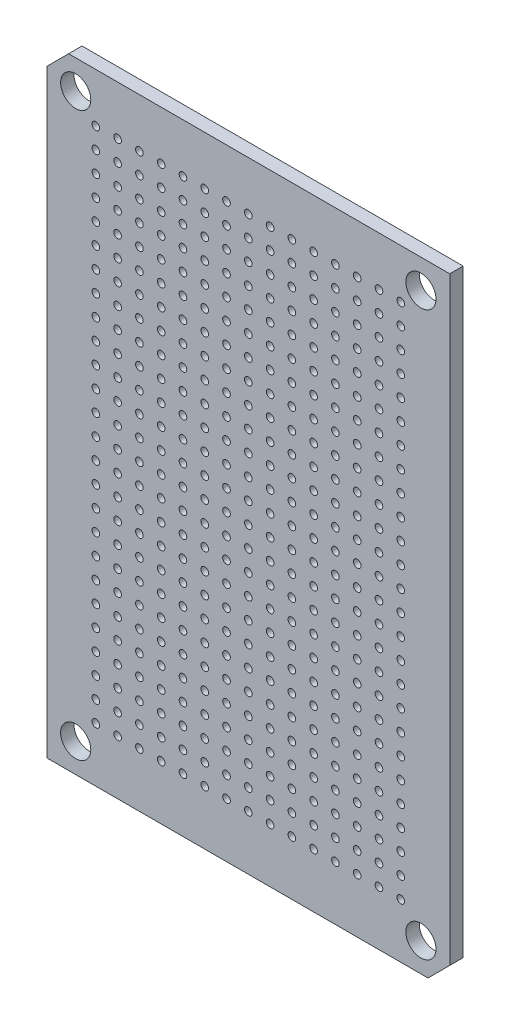
SolidWorks part; units mm, degrees
ref_plane "Front Plane" through (0, 0, 0) normal (0, 0, 1) x (1, 0, 0)
ref_plane "Top Plane" through (0, 0, 0) normal (0, 1, 0) x (1, 0, 0)
ref_plane "Right Plane" through (0, 0, 0) normal (1, 0, 0) x (0, 0, -1)
sketch "Sketch1" plane through (0, 0, 0) normal (0, 0, 1) x (1, 0, 0)
  line L0 (46.99, 72.39) -> (0, 0) construction
  line L1 (0, 0) -> (44.45, 0)
  line L2 (0, 0) -> (0, 69.85)
  line L3 (2.54, 72.39) -> (46.99, 72.39)
  line L4 (46.99, 2.54) -> (46.99, 72.39)
  line L5 (0, 72.39) -> (46.99, 0) construction
  line L6 (44.45, 0) -> (46.99, 2.54)
  line L7 (3.3655, 69.0245) -> (43.6245, 69.0245) construction
  line L8 (3.3655, 69.0245) -> (3.3655, 3.3655) construction
  line L9 (3.3655, 3.3655) -> (43.6245, 3.3655) construction
  line L10 (43.6245, 69.0245) -> (43.6245, 3.3655) construction
  line L11 (3.3655, 69.0245) -> (43.6245, 3.3655) construction
  line L12 (3.3655, 3.3655) -> (43.6245, 69.0245) construction
  line L13 (0, 69.85) -> (2.54, 72.39)
  circle A0 centre (3.3655, 69.0245) radius 1.7589
  circle A1 centre (43.6245, 69.0245) radius 1.759
  circle A2 centre (43.6245, 3.3655) radius 1.759
  circle A3 centre (3.3655, 3.3655) radius 1.7589
  point P5 (23.495, 36.195)
  point P13 (44.1061, 69.0245)
  point P15 (44.1933, 4.3085)
  point P17 (4.5521, 3.3655)
  dimension "D5" = 3.5179
  dimension "D1" = 46.99
  dimension "D2" = 72.39
  dimension "D3" = 40.259
  dimension "D4" = 65.659
extrude "Boss-Extrude1" add sketch "Sketch1" along normal blind 1.5621
sketch "Sketch2" plane through (0, 0, 1.5621) normal (0, 0, 1) x (1, 0, 0)
  line L0 (0, 69.85) -> (0, 0) construction
  line L1 (46.99, 72.39) -> (2.54, 72.39) construction
  circle A0 centre (5.715, 66.675) radius 0.4445
  circle A1 centre (8.255, 66.675) radius 0.4445
  circle A2 centre (10.795, 66.675) radius 0.4445
  circle A3 centre (13.335, 66.675) radius 0.4445
  circle A4 centre (15.875, 66.675) radius 0.4445
  circle A5 centre (18.415, 66.675) radius 0.4445
  circle A6 centre (20.955, 66.675) radius 0.4445
  circle A7 centre (23.495, 66.675) radius 0.4445
  circle A8 centre (26.035, 66.675) radius 0.4445
  circle A9 centre (28.575, 66.675) radius 0.4445
  circle A10 centre (31.115, 66.675) radius 0.4445
  circle A11 centre (33.655, 66.675) radius 0.4445
  circle A12 centre (36.195, 66.675) radius 0.4445
  circle A13 centre (38.735, 66.675) radius 0.4445
  circle A14 centre (41.275, 66.675) radius 0.4445
  circle A15 centre (8.255, 64.262) radius 0.4445
  circle A16 centre (10.795, 64.262) radius 0.4445
  circle A17 centre (13.335, 64.262) radius 0.4445
  circle A18 centre (15.875, 64.262) radius 0.4445
  circle A19 centre (18.415, 64.262) radius 0.4445
  circle A20 centre (20.955, 64.262) radius 0.4445
  circle A21 centre (23.495, 64.262) radius 0.4445
  circle A22 centre (26.035, 64.262) radius 0.4445
  circle A23 centre (28.575, 64.262) radius 0.4445
  circle A24 centre (31.115, 64.262) radius 0.4445
  circle A25 centre (33.655, 64.262) radius 0.4445
  circle A26 centre (36.195, 64.262) radius 0.4445
  circle A27 centre (38.735, 64.262) radius 0.4445
  circle A28 centre (41.275, 64.262) radius 0.4445
  circle A29 centre (8.255, 61.849) radius 0.4445
  circle A30 centre (10.795, 61.849) radius 0.4445
  circle A31 centre (13.335, 61.849) radius 0.4445
  circle A32 centre (15.875, 61.849) radius 0.4445
  circle A33 centre (18.415, 61.849) radius 0.4445
  circle A34 centre (20.955, 61.849) radius 0.4445
  circle A35 centre (23.495, 61.849) radius 0.4445
  circle A36 centre (26.035, 61.849) radius 0.4445
  circle A37 centre (28.575, 61.849) radius 0.4445
  circle A38 centre (31.115, 61.849) radius 0.4445
  circle A39 centre (33.655, 61.849) radius 0.4445
  circle A40 centre (36.195, 61.849) radius 0.4445
  circle A41 centre (38.735, 61.849) radius 0.4445
  circle A42 centre (41.275, 61.849) radius 0.4445
  circle A43 centre (8.255, 59.436) radius 0.4445
  circle A44 centre (10.795, 59.436) radius 0.4445
  circle A45 centre (13.335, 59.436) radius 0.4445
  circle A46 centre (15.875, 59.436) radius 0.4445
  circle A47 centre (18.415, 59.436) radius 0.4445
  circle A48 centre (20.955, 59.436) radius 0.4445
  circle A49 centre (23.495, 59.436) radius 0.4445
  circle A50 centre (26.035, 59.436) radius 0.4445
  circle A51 centre (28.575, 59.436) radius 0.4445
  circle A52 centre (31.115, 59.436) radius 0.4445
  circle A53 centre (33.655, 59.436) radius 0.4445
  circle A54 centre (36.195, 59.436) radius 0.4445
  circle A55 centre (38.735, 59.436) radius 0.4445
  circle A56 centre (41.275, 59.436) radius 0.4445
  circle A57 centre (8.255, 57.023) radius 0.4445
  circle A58 centre (10.795, 57.023) radius 0.4445
  circle A59 centre (13.335, 57.023) radius 0.4445
  circle A60 centre (15.875, 57.023) radius 0.4445
  circle A61 centre (18.415, 57.023) radius 0.4445
  circle A62 centre (20.955, 57.023) radius 0.4445
  circle A63 centre (23.495, 57.023) radius 0.4445
  circle A64 centre (26.035, 57.023) radius 0.4445
  circle A65 centre (28.575, 57.023) radius 0.4445
  circle A66 centre (31.115, 57.023) radius 0.4445
  circle A67 centre (33.655, 57.023) radius 0.4445
  circle A68 centre (36.195, 57.023) radius 0.4445
  circle A69 centre (38.735, 57.023) radius 0.4445
  circle A70 centre (41.275, 57.023) radius 0.4445
  circle A71 centre (8.255, 54.61) radius 0.4445
  circle A72 centre (10.795, 54.61) radius 0.4445
  circle A73 centre (13.335, 54.61) radius 0.4445
  circle A74 centre (15.875, 54.61) radius 0.4445
  circle A75 centre (18.415, 54.61) radius 0.4445
  circle A76 centre (20.955, 54.61) radius 0.4445
  circle A77 centre (23.495, 54.61) radius 0.4445
  circle A78 centre (26.035, 54.61) radius 0.4445
  circle A79 centre (28.575, 54.61) radius 0.4445
  circle A80 centre (31.115, 54.61) radius 0.4445
  circle A81 centre (33.655, 54.61) radius 0.4445
  circle A82 centre (36.195, 54.61) radius 0.4445
  circle A83 centre (38.735, 54.61) radius 0.4445
  circle A84 centre (41.275, 54.61) radius 0.4445
  circle A85 centre (8.255, 52.197) radius 0.4445
  circle A86 centre (10.795, 52.197) radius 0.4445
  circle A87 centre (13.335, 52.197) radius 0.4445
  circle A88 centre (15.875, 52.197) radius 0.4445
  circle A89 centre (18.415, 52.197) radius 0.4445
  circle A90 centre (20.955, 52.197) radius 0.4445
  circle A91 centre (23.495, 52.197) radius 0.4445
  circle A92 centre (26.035, 52.197) radius 0.4445
  circle A93 centre (28.575, 52.197) radius 0.4445
  circle A94 centre (31.115, 52.197) radius 0.4445
  circle A95 centre (33.655, 52.197) radius 0.4445
  circle A96 centre (36.195, 52.197) radius 0.4445
  circle A97 centre (38.735, 52.197) radius 0.4445
  circle A98 centre (41.275, 52.197) radius 0.4445
  circle A99 centre (8.255, 49.784) radius 0.4445
  circle A100 centre (10.795, 49.784) radius 0.4445
  circle A101 centre (13.335, 49.784) radius 0.4445
  circle A102 centre (15.875, 49.784) radius 0.4445
  circle A103 centre (18.415, 49.784) radius 0.4445
  circle A104 centre (20.955, 49.784) radius 0.4445
  circle A105 centre (23.495, 49.784) radius 0.4445
  circle A106 centre (26.035, 49.784) radius 0.4445
  circle A107 centre (28.575, 49.784) radius 0.4445
  circle A108 centre (31.115, 49.784) radius 0.4445
  circle A109 centre (33.655, 49.784) radius 0.4445
  circle A110 centre (36.195, 49.784) radius 0.4445
  circle A111 centre (38.735, 49.784) radius 0.4445
  circle A112 centre (41.275, 49.784) radius 0.4445
  circle A113 centre (8.255, 47.371) radius 0.4445
  circle A114 centre (10.795, 47.371) radius 0.4445
  circle A115 centre (13.335, 47.371) radius 0.4445
  circle A116 centre (15.875, 47.371) radius 0.4445
  circle A117 centre (18.415, 47.371) radius 0.4445
  circle A118 centre (20.955, 47.371) radius 0.4445
  circle A119 centre (23.495, 47.371) radius 0.4445
  circle A120 centre (26.035, 47.371) radius 0.4445
  circle A121 centre (28.575, 47.371) radius 0.4445
  circle A122 centre (31.115, 47.371) radius 0.4445
  circle A123 centre (33.655, 47.371) radius 0.4445
  circle A124 centre (36.195, 47.371) radius 0.4445
  circle A125 centre (38.735, 47.371) radius 0.4445
  circle A126 centre (41.275, 47.371) radius 0.4445
  circle A127 centre (8.255, 44.958) radius 0.4445
  circle A128 centre (10.795, 44.958) radius 0.4445
  circle A129 centre (13.335, 44.958) radius 0.4445
  circle A130 centre (15.875, 44.958) radius 0.4445
  circle A131 centre (18.415, 44.958) radius 0.4445
  circle A132 centre (20.955, 44.958) radius 0.4445
  circle A133 centre (23.495, 44.958) radius 0.4445
  circle A134 centre (26.035, 44.958) radius 0.4445
  circle A135 centre (28.575, 44.958) radius 0.4445
  circle A136 centre (31.115, 44.958) radius 0.4445
  circle A137 centre (33.655, 44.958) radius 0.4445
  circle A138 centre (36.195, 44.958) radius 0.4445
  circle A139 centre (38.735, 44.958) radius 0.4445
  circle A140 centre (41.275, 44.958) radius 0.4445
  circle A141 centre (8.255, 42.545) radius 0.4445
  circle A142 centre (10.795, 42.545) radius 0.4445
  circle A143 centre (13.335, 42.545) radius 0.4445
  circle A144 centre (15.875, 42.545) radius 0.4445
  circle A145 centre (18.415, 42.545) radius 0.4445
  circle A146 centre (20.955, 42.545) radius 0.4445
  circle A147 centre (23.495, 42.545) radius 0.4445
  circle A148 centre (26.035, 42.545) radius 0.4445
  circle A149 centre (28.575, 42.545) radius 0.4445
  circle A150 centre (31.115, 42.545) radius 0.4445
  circle A151 centre (33.655, 42.545) radius 0.4445
  circle A152 centre (36.195, 42.545) radius 0.4445
  circle A153 centre (38.735, 42.545) radius 0.4445
  circle A154 centre (41.275, 42.545) radius 0.4445
  circle A155 centre (8.255, 40.132) radius 0.4445
  circle A156 centre (10.795, 40.132) radius 0.4445
  circle A157 centre (13.335, 40.132) radius 0.4445
  circle A158 centre (15.875, 40.132) radius 0.4445
  circle A159 centre (18.415, 40.132) radius 0.4445
  circle A160 centre (20.955, 40.132) radius 0.4445
  circle A161 centre (23.495, 40.132) radius 0.4445
  circle A162 centre (26.035, 40.132) radius 0.4445
  circle A163 centre (28.575, 40.132) radius 0.4445
  circle A164 centre (31.115, 40.132) radius 0.4445
  circle A165 centre (33.655, 40.132) radius 0.4445
  circle A166 centre (36.195, 40.132) radius 0.4445
  circle A167 centre (38.735, 40.132) radius 0.4445
  circle A168 centre (41.275, 40.132) radius 0.4445
  circle A169 centre (8.255, 37.719) radius 0.4445
  circle A170 centre (10.795, 37.719) radius 0.4445
  circle A171 centre (13.335, 37.719) radius 0.4445
  circle A172 centre (15.875, 37.719) radius 0.4445
  circle A173 centre (18.415, 37.719) radius 0.4445
  circle A174 centre (20.955, 37.719) radius 0.4445
  circle A175 centre (23.495, 37.719) radius 0.4445
  circle A176 centre (26.035, 37.719) radius 0.4445
  circle A177 centre (28.575, 37.719) radius 0.4445
  circle A178 centre (31.115, 37.719) radius 0.4445
  circle A179 centre (33.655, 37.719) radius 0.4445
  circle A180 centre (36.195, 37.719) radius 0.4445
  circle A181 centre (38.735, 37.719) radius 0.4445
  circle A182 centre (41.275, 37.719) radius 0.4445
  circle A183 centre (8.255, 35.306) radius 0.4445
  circle A184 centre (10.795, 35.306) radius 0.4445
  circle A185 centre (13.335, 35.306) radius 0.4445
  circle A186 centre (15.875, 35.306) radius 0.4445
  circle A187 centre (18.415, 35.306) radius 0.4445
  circle A188 centre (20.955, 35.306) radius 0.4445
  circle A189 centre (23.495, 35.306) radius 0.4445
  circle A190 centre (26.035, 35.306) radius 0.4445
  circle A191 centre (28.575, 35.306) radius 0.4445
  circle A192 centre (31.115, 35.306) radius 0.4445
  circle A193 centre (33.655, 35.306) radius 0.4445
  circle A194 centre (36.195, 35.306) radius 0.4445
  circle A195 centre (38.735, 35.306) radius 0.4445
  circle A196 centre (41.275, 35.306) radius 0.4445
  circle A197 centre (8.255, 32.893) radius 0.4445
  circle A198 centre (10.795, 32.893) radius 0.4445
  circle A199 centre (13.335, 32.893) radius 0.4445
  circle A200 centre (15.875, 32.893) radius 0.4445
  circle A201 centre (18.415, 32.893) radius 0.4445
  circle A202 centre (20.955, 32.893) radius 0.4445
  circle A203 centre (23.495, 32.893) radius 0.4445
  circle A204 centre (26.035, 32.893) radius 0.4445
  circle A205 centre (28.575, 32.893) radius 0.4445
  circle A206 centre (31.115, 32.893) radius 0.4445
  circle A207 centre (33.655, 32.893) radius 0.4445
  circle A208 centre (36.195, 32.893) radius 0.4445
  circle A209 centre (38.735, 32.893) radius 0.4445
  circle A210 centre (41.275, 32.893) radius 0.4445
  circle A211 centre (8.255, 30.48) radius 0.4445
  circle A212 centre (10.795, 30.48) radius 0.4445
  circle A213 centre (13.335, 30.48) radius 0.4445
  circle A214 centre (15.875, 30.48) radius 0.4445
  circle A215 centre (18.415, 30.48) radius 0.4445
  circle A216 centre (20.955, 30.48) radius 0.4445
  circle A217 centre (23.495, 30.48) radius 0.4445
  circle A218 centre (26.035, 30.48) radius 0.4445
  circle A219 centre (28.575, 30.48) radius 0.4445
  circle A220 centre (31.115, 30.48) radius 0.4445
  circle A221 centre (33.655, 30.48) radius 0.4445
  circle A222 centre (36.195, 30.48) radius 0.4445
  circle A223 centre (38.735, 30.48) radius 0.4445
  circle A224 centre (41.275, 30.48) radius 0.4445
  circle A225 centre (8.255, 28.067) radius 0.4445
  circle A226 centre (10.795, 28.067) radius 0.4445
  circle A227 centre (13.335, 28.067) radius 0.4445
  circle A228 centre (15.875, 28.067) radius 0.4445
  circle A229 centre (18.415, 28.067) radius 0.4445
  circle A230 centre (20.955, 28.067) radius 0.4445
  circle A231 centre (23.495, 28.067) radius 0.4445
  circle A232 centre (26.035, 28.067) radius 0.4445
  circle A233 centre (28.575, 28.067) radius 0.4445
  circle A234 centre (31.115, 28.067) radius 0.4445
  circle A235 centre (33.655, 28.067) radius 0.4445
  circle A236 centre (36.195, 28.067) radius 0.4445
  circle A237 centre (38.735, 28.067) radius 0.4445
  circle A238 centre (41.275, 28.067) radius 0.4445
  circle A239 centre (8.255, 25.654) radius 0.4445
  circle A240 centre (10.795, 25.654) radius 0.4445
  circle A241 centre (13.335, 25.654) radius 0.4445
  circle A242 centre (15.875, 25.654) radius 0.4445
  circle A243 centre (18.415, 25.654) radius 0.4445
  circle A244 centre (20.955, 25.654) radius 0.4445
  circle A245 centre (23.495, 25.654) radius 0.4445
  circle A246 centre (26.035, 25.654) radius 0.4445
  circle A247 centre (28.575, 25.654) radius 0.4445
  circle A248 centre (31.115, 25.654) radius 0.4445
  circle A249 centre (33.655, 25.654) radius 0.4445
  circle A250 centre (36.195, 25.654) radius 0.4445
  circle A251 centre (38.735, 25.654) radius 0.4445
  circle A252 centre (41.275, 25.654) radius 0.4445
  circle A253 centre (8.255, 23.241) radius 0.4445
  circle A254 centre (10.795, 23.241) radius 0.4445
  circle A255 centre (13.335, 23.241) radius 0.4445
  circle A256 centre (15.875, 23.241) radius 0.4445
  circle A257 centre (18.415, 23.241) radius 0.4445
  circle A258 centre (20.955, 23.241) radius 0.4445
  circle A259 centre (23.495, 23.241) radius 0.4445
  circle A260 centre (26.035, 23.241) radius 0.4445
  circle A261 centre (28.575, 23.241) radius 0.4445
  circle A262 centre (31.115, 23.241) radius 0.4445
  circle A263 centre (33.655, 23.241) radius 0.4445
  circle A264 centre (36.195, 23.241) radius 0.4445
  circle A265 centre (38.735, 23.241) radius 0.4445
  circle A266 centre (41.275, 23.241) radius 0.4445
  circle A267 centre (8.255, 20.828) radius 0.4445
  circle A268 centre (10.795, 20.828) radius 0.4445
  circle A269 centre (13.335, 20.828) radius 0.4445
  circle A270 centre (15.875, 20.828) radius 0.4445
  circle A271 centre (18.415, 20.828) radius 0.4445
  circle A272 centre (20.955, 20.828) radius 0.4445
  circle A273 centre (23.495, 20.828) radius 0.4445
  circle A274 centre (26.035, 20.828) radius 0.4445
  circle A275 centre (28.575, 20.828) radius 0.4445
  circle A276 centre (31.115, 20.828) radius 0.4445
  circle A277 centre (33.655, 20.828) radius 0.4445
  circle A278 centre (36.195, 20.828) radius 0.4445
  circle A279 centre (38.735, 20.828) radius 0.4445
  circle A280 centre (41.275, 20.828) radius 0.4445
  circle A281 centre (8.255, 18.415) radius 0.4445
  circle A282 centre (10.795, 18.415) radius 0.4445
  circle A283 centre (13.335, 18.415) radius 0.4445
  circle A284 centre (15.875, 18.415) radius 0.4445
  circle A285 centre (18.415, 18.415) radius 0.4445
  circle A286 centre (20.955, 18.415) radius 0.4445
  circle A287 centre (23.495, 18.415) radius 0.4445
  circle A288 centre (26.035, 18.415) radius 0.4445
  circle A289 centre (28.575, 18.415) radius 0.4445
  circle A290 centre (31.115, 18.415) radius 0.4445
  circle A291 centre (33.655, 18.415) radius 0.4445
  circle A292 centre (36.195, 18.415) radius 0.4445
  circle A293 centre (38.735, 18.415) radius 0.4445
  circle A294 centre (41.275, 18.415) radius 0.4445
  circle A295 centre (8.255, 16.002) radius 0.4445
  circle A296 centre (10.795, 16.002) radius 0.4445
  circle A297 centre (13.335, 16.002) radius 0.4445
  circle A298 centre (15.875, 16.002) radius 0.4445
  circle A299 centre (18.415, 16.002) radius 0.4445
  circle A300 centre (20.955, 16.002) radius 0.4445
  circle A301 centre (23.495, 16.002) radius 0.4445
  circle A302 centre (26.035, 16.002) radius 0.4445
  circle A303 centre (28.575, 16.002) radius 0.4445
  circle A304 centre (31.115, 16.002) radius 0.4445
  circle A305 centre (33.655, 16.002) radius 0.4445
  circle A306 centre (36.195, 16.002) radius 0.4445
  circle A307 centre (38.735, 16.002) radius 0.4445
  circle A308 centre (41.275, 16.002) radius 0.4445
  circle A309 centre (8.255, 13.589) radius 0.4445
  circle A310 centre (10.795, 13.589) radius 0.4445
  circle A311 centre (13.335, 13.589) radius 0.4445
  circle A312 centre (15.875, 13.589) radius 0.4445
  circle A313 centre (18.415, 13.589) radius 0.4445
  circle A314 centre (20.955, 13.589) radius 0.4445
  circle A315 centre (23.495, 13.589) radius 0.4445
  circle A316 centre (26.035, 13.589) radius 0.4445
  circle A317 centre (28.575, 13.589) radius 0.4445
  circle A318 centre (31.115, 13.589) radius 0.4445
  circle A319 centre (33.655, 13.589) radius 0.4445
  circle A320 centre (36.195, 13.589) radius 0.4445
  circle A321 centre (38.735, 13.589) radius 0.4445
  circle A322 centre (41.275, 13.589) radius 0.4445
  circle A323 centre (8.255, 11.176) radius 0.4445
  circle A324 centre (10.795, 11.176) radius 0.4445
  circle A325 centre (13.335, 11.176) radius 0.4445
  circle A326 centre (15.875, 11.176) radius 0.4445
  circle A327 centre (18.415, 11.176) radius 0.4445
  circle A328 centre (20.955, 11.176) radius 0.4445
  circle A329 centre (23.495, 11.176) radius 0.4445
  circle A330 centre (26.035, 11.176) radius 0.4445
  circle A331 centre (28.575, 11.176) radius 0.4445
  circle A332 centre (31.115, 11.176) radius 0.4445
  circle A333 centre (33.655, 11.176) radius 0.4445
  circle A334 centre (36.195, 11.176) radius 0.4445
  circle A335 centre (38.735, 11.176) radius 0.4445
  circle A336 centre (41.275, 11.176) radius 0.4445
  circle A337 centre (8.255, 8.763) radius 0.4445
  circle A338 centre (10.795, 8.763) radius 0.4445
  circle A339 centre (13.335, 8.763) radius 0.4445
  circle A340 centre (15.875, 8.763) radius 0.4445
  circle A341 centre (18.415, 8.763) radius 0.4445
  circle A342 centre (20.955, 8.763) radius 0.4445
  circle A343 centre (23.495, 8.763) radius 0.4445
  circle A344 centre (26.035, 8.763) radius 0.4445
  circle A345 centre (28.575, 8.763) radius 0.4445
  circle A346 centre (31.115, 8.763) radius 0.4445
  circle A347 centre (33.655, 8.763) radius 0.4445
  circle A348 centre (36.195, 8.763) radius 0.4445
  circle A349 centre (38.735, 8.763) radius 0.4445
  circle A350 centre (41.275, 8.763) radius 0.4445
  circle A351 centre (8.255, 6.35) radius 0.4445
  circle A352 centre (10.795, 6.35) radius 0.4445
  circle A353 centre (13.335, 6.35) radius 0.4445
  circle A354 centre (15.875, 6.35) radius 0.4445
  circle A355 centre (18.415, 6.35) radius 0.4445
  circle A356 centre (20.955, 6.35) radius 0.4445
  circle A357 centre (23.495, 6.35) radius 0.4445
  circle A358 centre (26.035, 6.35) radius 0.4445
  circle A359 centre (28.575, 6.35) radius 0.4445
  circle A360 centre (31.115, 6.35) radius 0.4445
  circle A361 centre (33.655, 6.35) radius 0.4445
  circle A362 centre (36.195, 6.35) radius 0.4445
  circle A363 centre (38.735, 6.35) radius 0.4445
  circle A364 centre (41.275, 6.35) radius 0.4445
  circle A365 centre (5.715, 64.262) radius 0.4445
  circle A366 centre (5.715, 61.849) radius 0.4445
  circle A367 centre (5.715, 59.436) radius 0.4445
  circle A368 centre (5.715, 57.023) radius 0.4445
  circle A369 centre (5.715, 54.61) radius 0.4445
  circle A370 centre (5.715, 52.197) radius 0.4445
  circle A371 centre (5.715, 49.784) radius 0.4445
  circle A372 centre (5.715, 47.371) radius 0.4445
  circle A373 centre (5.715, 44.958) radius 0.4445
  circle A374 centre (5.715, 42.545) radius 0.4445
  circle A375 centre (5.715, 40.132) radius 0.4445
  circle A376 centre (5.715, 37.719) radius 0.4445
  circle A377 centre (5.715, 35.306) radius 0.4445
  circle A378 centre (5.715, 32.893) radius 0.4445
  circle A379 centre (5.715, 30.48) radius 0.4445
  circle A380 centre (5.715, 28.067) radius 0.4445
  circle A381 centre (5.715, 25.654) radius 0.4445
  circle A382 centre (5.715, 23.241) radius 0.4445
  circle A383 centre (5.715, 20.828) radius 0.4445
  circle A384 centre (5.715, 18.415) radius 0.4445
  circle A385 centre (5.715, 16.002) radius 0.4445
  circle A386 centre (5.715, 13.589) radius 0.4445
  circle A387 centre (5.715, 11.176) radius 0.4445
  circle A388 centre (5.715, 8.763) radius 0.4445
  circle A389 centre (5.715, 6.35) radius 0.4445
  dimension "D1" = 0.889
  dimension "D2" = 5.715
  dimension "D3" = 5.715
  dimension "D4" = 15
  dimension "D5" = 26
extrude "Cut-Extrude1" cut sketch "Sketch2" against normal up to surface (1.5621 mm away) up to face at (45.3835, 3.3655, 0)
